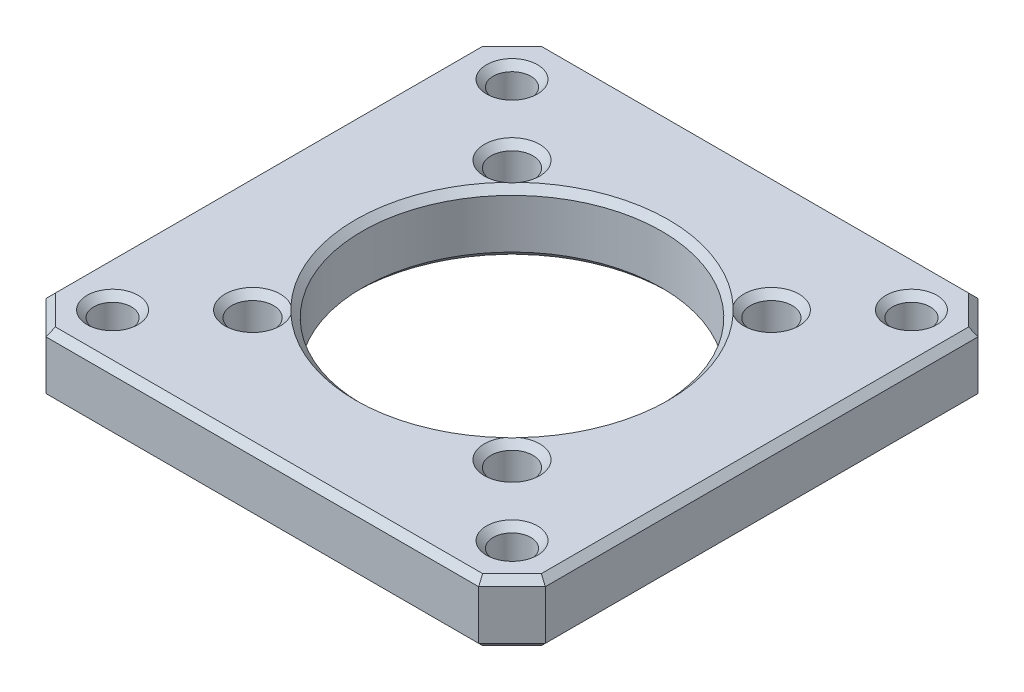
SolidWorks part; units mm, degrees
material "Alum Plate"
ref_plane "Front Plane" through (0, 0, 0) normal (0, 0, 1) x (1, 0, 0)
ref_plane "Top Plane" through (0, 0, 0) normal (0, 1, 0) x (1, 0, 0)
ref_plane "Right Plane" through (0, 0, 0) normal (1, 0, 0) x (0, 0, -1)
other "Bounding Box"
ref_plane "Default Plane" through (0, 2.286, 19.05) normal (0, -1, 0) x (-1, 0, 0)
sketch "Sketch1" plane through (0, 0, 0) normal (0, 1, 0) x (1, 0, 0)
  line L1 (-19.05, 19.05) -> (19.05, 19.05)
  line L2 (-19.05, 19.05) -> (-19.05, -19.05)
  line L3 (-19.05, -19.05) -> (19.05, -19.05)
  line L4 (19.05, 19.05) -> (19.05, -19.05)
  line L5 (-19.05, 19.05) -> (19.05, -19.05) construction
  line L6 (-19.05, -19.05) -> (19.05, 19.05) construction
  circle A0 centre (0, 0) radius 11.43
  point P0 (0, 0)
  dimension "D2" = 22.86
  dimension "D1" = 38.1
extrude "Boss-Extrude1" add sketch "Sketch1" along normal blind 4.7625
sketch "Sketch2" plane through (0, 4.7625, 0) normal (0, 1, 0) x (1, 0, 0)
  line L0 (0, 0) -> (9.8962, 9.8962) construction
  line L1 (0, 0) -> (15.24, 15.24) construction
  line L2 (15.24, 15.24) -> (19.05, 15.24) construction
  line L3 (19.05, -19.05) -> (19.05, 19.05) construction
  line L4 (15.24, 15.24) -> (15.24, 19.05) construction
  line L5 (19.05, 19.05) -> (-19.05, 19.05) construction
  circle A0 centre (9.8962, 9.8962) radius 1.6002
  circle A1 centre (15.24, 15.24) radius 1.4351
  dimension "D1" = 3.2004
  dimension "D3" = 2.8702
  dimension "D2" = 13.9954
  dimension "D4" = 3.81
extrude "Cut-Extrude1" cut sketch "Sketch2" against normal through all
pattern_circular "CirPattern1" count 4 over 360 about axis through (0, 4.7625, 0) along (0, -1, 0) of "Cut-Extrude1"
chamfer "Chamfer1" distance 2.54 angle 45 4 edges at (-19.05, 2.3813, 19.05) (19.05, 2.3813, 19.05) (19.05, 2.3813, -19.05) (-19.05, 2.3813, -19.05)
chamfer "Chamfer2" distance 0.508 angle 45 34 edges at (0, 0, 11.43) (17.78, 0, 17.78) (19.05, 0, 0) (17.78, 0, -17.78) (0, 0, -19.05) (-17.78, 0, -17.78) (-19.05, 0, 0) (-17.78, 0, 17.78) (0, 0, 19.05) (15.24, 0, -13.8049) (9.8962, 0, -8.296) (8.296, 0, 9.8962) (-8.296, 0, -9.8962) (-15.24, 0, 13.8049) (-9.8962, 0, 8.296) (13.8049, 0, 15.24) (-13.8049, 0, -15.24) (0, 4.7625, 11.43) (-17.78, 4.7625, -17.78) (0, 4.7625, -19.05) (17.78, 4.7625, -17.78) (19.05, 4.7625, 0) (17.78, 4.7625, 17.78) (0, 4.7625, 19.05) (-17.78, 4.7625, 17.78) (-19.05, 4.7625, 0) (15.24, 4.7625, -13.8049) (9.8962, 4.7625, -8.296) (8.296, 4.7625, 9.8962) (-8.296, 4.7625, -9.8962) (-15.24, 4.7625, 13.8049) (-9.8962, 4.7625, 8.296) (13.8049, 4.7625, 15.24) (-13.8049, 4.7625, -15.24)
equation "\"Unit Measure\"= \"BoundingVolume\" / \"Thickness\"'in^2"
